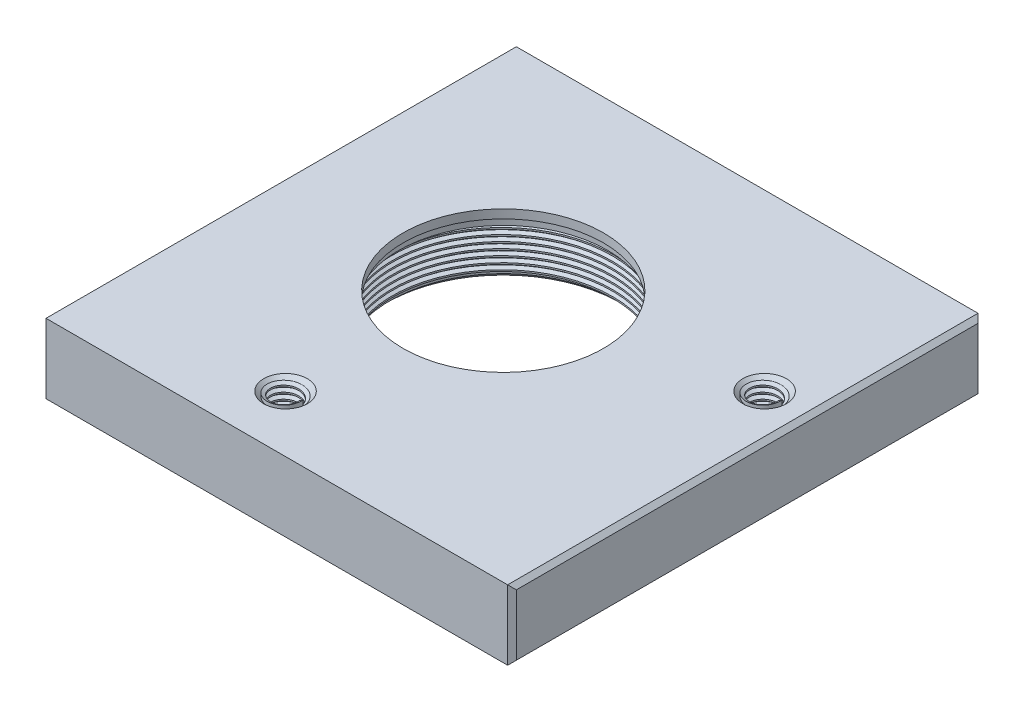
SolidWorks part; units mm, degrees
material "1060 Сплав"
ref_plane "Спереди" through (0, 0, 0) normal (0, 0, 1) x (1, 0, 0)
ref_plane "Сверху" through (0, 0, 0) normal (0, 1, 0) x (1, 0, 0)
ref_plane "Справа" through (0, 0, 0) normal (1, 0, 0) x (0, 0, -1)
sketch "Эскиз1" plane through (0, 0, 0) normal (0, 1, 0) x (1, 0, 0)
  line L1 (-25.189, 30.375) -> (28.811, 30.375)
  line L2 (-25.189, 30.375) -> (-25.189, -23.625)
  line L3 (-25.189, -23.625) -> (28.811, -23.625)
  line L4 (28.811, 30.375) -> (28.811, -23.625)
  circle A0 centre (-1.189, 5.375) radius 11.5
  circle A1 centre (23.811, 10.375) radius 2
  circle A2 centre (-3.689, -17.125) radius 2
  dimension "D3" = 23
  dimension "D4" = 25
  dimension "D5" = 24
  dimension "D6" = 4
  dimension "D7" = 4
  dimension "D8" = 6.5
  dimension "D9" = 5
  dimension "D10" = 21.5
  dimension "D11" = 20
  dimension "D1" = 54
  dimension "D2" = 54
extrude "Бобышка-Вытянуть1" add sketch "Эскиз1" along normal blind 8
chamfer "Фаска1" distance 0.5 angle 45 12 edges at (-25.189, 4, 23.625) (-25.189, 0, -3.375) (-25.189, 4, -30.375) (-25.189, 8, -3.375) (28.811, 4, 23.625) (28.811, 0, -3.375) (28.811, 4, -30.375) (28.811, 8, -3.375) (-3.689, 0, 19.125) (23.811, 0, -8.375) (-3.689, 8, 19.125) (23.811, 8, -8.375)
sketch "Эскиз2" plane through (0, 0, 0) normal (0, -1, 0) x (1, 0, 0)
  circle A0 centre (-1.189, -5.375) radius 13
extrude "Вырез-Вытянуть1" cut sketch "Эскиз2" against normal blind 6
sketch "Эскиз3" plane through (0, 6, 0) normal (0, -1, 0) x (1, 0, 0)
  circle A0 centre (-1.189, -5.375) radius 12
extrude "Вырез-Вытянуть2" cut sketch "Эскиз3" against normal blind 1
chamfer "Фаска2" distance 0.5 angle 45 1 edges at (-1.189, 0, -18.375)
thread "Резьба1" pitch 0.7 start angle 0, offset 0, length 6, pitch 0.7, diameter 26
ref_plane "Плоскость1" through (11.811, 0.5, -5.375) normal (0, 0, 1) x (1, 0, 0)
sketch "Профиль резьбы1" plane through (11.811, 0.5, -5.375) normal (0, 0, 1) x (1, 0, 0)
  line L0 (0, 0) -> (0, 0.7) construction
  line L11 (0, 0) -> (0, 0.6125)
  line L12 (0, 0.6125) -> (-0.3789, 0.3937)
  line L13 (-0.3789, 0.3937) -> (-0.3789, 0.2187)
  line L15 (-0.3789, 0.2187) -> (0, 0)
  line L17 (-0.3789, 0.3062) -> (0, 0.3062) construction
  point P2 (0, 0)
  dimension "Pitch" = 0.7
  dimension "Profile_Angle" = 60
  dimension "Profile_Land" = 0.175
  dimension "Profile_Height" = 0.3789
thread "Резьба2" pitch 0.7 profile "Профиль резьбы2" start angle 0, offset 0, length 7, pitch 0.7, diameter 4
ref_plane "Плоскость2" through (-1.689, 0.5, 17.125) normal (0, 0, 1) x (1, 0, 0)
sketch "Профиль резьбы2" plane through (-1.689, 0.5, 17.125) normal (0, 0, 1) x (1, 0, 0)
  line L0 (0, 0) -> (0, 0.7) construction
  line L11 (0, 0) -> (0, 0.6125)
  line L12 (0, 0.6125) -> (-0.3789, 0.3937)
  line L13 (-0.3789, 0.3937) -> (-0.3789, 0.2187)
  line L15 (-0.3789, 0.2187) -> (0, 0)
  line L17 (-0.3789, 0.3062) -> (0, 0.3062) construction
  point P2 (0, 0)
  dimension "Pitch" = 0.7
  dimension "Profile_Angle" = 60
  dimension "Profile_Land" = 0.175
  dimension "Profile_Height" = 0.3789
thread "Резьба3" pitch 0.7 profile "Профиль резьбы3" start angle 0, offset 0, length 7, pitch 0.7, diameter 4
ref_plane "Плоскость3" through (25.811, 0.5, -10.375) normal (0, 0, 1) x (1, 0, 0)
sketch "Профиль резьбы3" plane through (25.811, 0.5, -10.375) normal (0, 0, 1) x (1, 0, 0)
  line L0 (0, 0) -> (0, 0.7) construction
  line L11 (0, 0) -> (0, 0.6125)
  line L12 (0, 0.6125) -> (-0.3789, 0.3937)
  line L13 (-0.3789, 0.3937) -> (-0.3789, 0.2187)
  line L15 (-0.3789, 0.2187) -> (0, 0)
  line L17 (-0.3789, 0.3062) -> (0, 0.3062) construction
  point P2 (0, 0)
  dimension "Pitch" = 0.7
  dimension "Profile_Angle" = 60
  dimension "Profile_Land" = 0.175
  dimension "Profile_Height" = 0.3789
